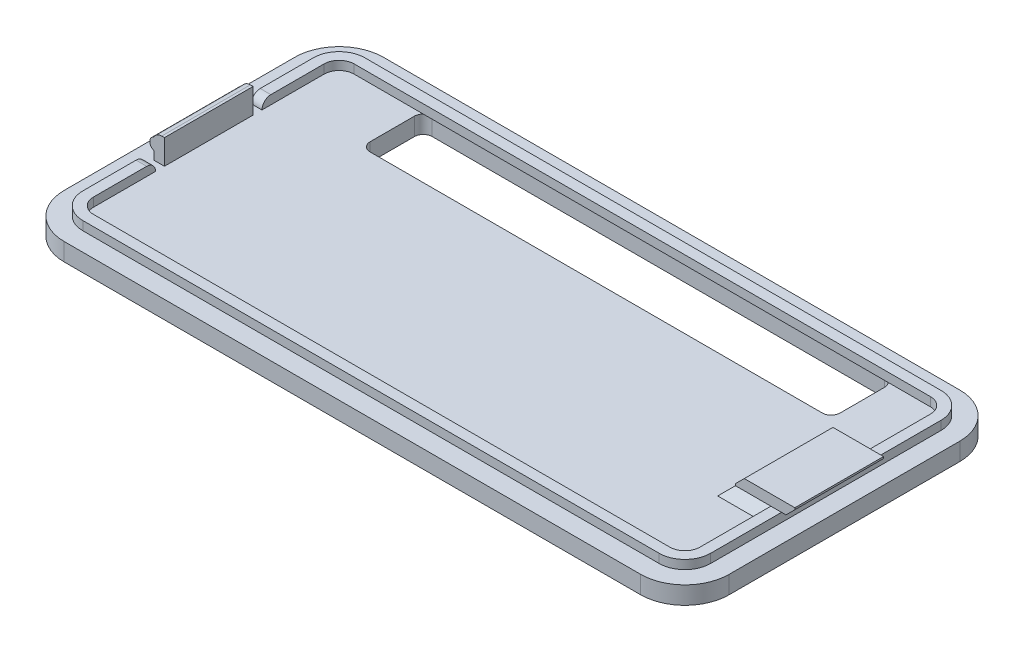
SolidWorks part; units mm, degrees
ref_plane "前视基准面" through (0, 0, 0) normal (0, 0, 1) x (1, 0, 0)
ref_plane "上视基准面" through (0, 0, 0) normal (0, 1, 0) x (1, 0, 0)
ref_plane "右视基准面" through (0, 0, 0) normal (1, 0, 0) x (0, 0, -1)
sketch "zero" plane through (0, 0, 0) normal (0, 1, 0) x (1, 0, 0)
  line L1 (-29.5, 15) -> (29.5, 15)
  line L2 (-32.5, 12) -> (-32.5, -12)
  line L3 (-29.5, -15) -> (29.5, -15)
  line L4 (32.5, 12) -> (32.5, -12)
  line L5 (-32.5, 15) -> (32.5, -15) construction
  line L6 (-32.5, -15) -> (32.5, 15) construction
  line L7 (-25.7, -15) -> (-14.5, -15)
  line L8 (-25.7, -15) -> (-25.7, -9.6569)
  line L9 (-25.7, -9.6569) -> (-14.5, -9.6569)
  line L10 (-14.5, -15) -> (-14.5, -9.6569)
  line L11 (5.2, -15) -> (12.7, -15)
  line L12 (5.2, -15) -> (5.2, -11)
  line L13 (5.2, -11) -> (12.7, -11)
  line L14 (12.7, -15) -> (12.7, -11)
  line L15 (17.8, -15) -> (25.3, -15)
  line L16 (17.8, -15) -> (17.8, -11)
  line L17 (17.8, -11) -> (25.3, -11)
  line L18 (25.3, -15) -> (25.3, -11)
  line L19 (-32.5, 7.7) -> (-19.5, 7.7)
  line L20 (-32.5, 7.7) -> (-32.5, -4.3)
  line L21 (-32.5, -4.3) -> (-19.5, -4.3)
  line L22 (-19.5, 7.7) -> (-19.5, -4.3)
  line L23 (-25.5, 14) -> (25.5, 14)
  line L24 (-25.5, 14) -> (-25.5, 8.8)
  line L25 (-25.5, 8.8) -> (25.5, 8.8)
  line L26 (25.5, 14) -> (25.5, 8.8)
  line L27 (-19.5, 7.2329) -> (-35.5, 7.2329)
  line L28 (-19.5, 7.2329) -> (-19.5, -3.7671)
  line L29 (-19.5, -3.7671) -> (-35.5, -3.7671)
  line L30 (-35.5, 7.2329) -> (-35.5, -3.7671)
  arc A0 (29.5, -15) -> (32.5, -12) centre (29.5, -12) ccw
  arc A1 (29.5, 15) -> (32.5, 12) centre (29.5, 12) cw
  arc A2 (-32.5, -12) -> (-29.5, -15) centre (-29.5, -12) ccw
  arc A3 (-29.5, 15) -> (-32.5, 12) centre (-29.5, 12) ccw
  circle A4 centre (-29, 11.4) radius 3
  circle A5 centre (-29, -11.5) radius 3
  circle A6 centre (29, 11.4) radius 3
  circle A7 centre (29, -11.5) radius 3
  circle A8 centre (-29, 11.4) radius 1.375
  circle A9 centre (-29, -11.5) radius 1.375
  circle A10 centre (29, -11.5) radius 1.375
  circle A11 centre (29, 11.4) radius 1.375
  point P0 (0, 0)
  dimension "D3" = 3
  dimension "D4" = 6
  dimension "D9" = 2.75
  dimension "D1" = 65
  dimension "D2" = 30
  dimension "D5" = 3.6
  dimension "D6" = 3.5
  dimension "D7" = 3.5
  dimension "D8" = 3.5
  dimension "D10" = 12
  dimension "D11" = 7.3
  dimension "D12" = 13
  dimension "D13" = 11.2
  dimension "D14" = 6.8
  dimension "D15" = 19.7
  dimension "D16" = 7.5
  dimension "D17" = 7.5
  dimension "D18" = 5.1
  dimension "D19" = 4
  dimension "D20" = 5.2
  dimension "D21" = 7
  dimension "D22" = 7
  dimension "D23" = 1
  dimension "D24" = 11
  dimension "D25" = 16
sketch "sugar" plane through (0, 0, 0) normal (0, 1, 0) x (1, 0, 0)
  line L1 (-29.5, 15) -> (29.5, 15)
  line L2 (-32.5, 12) -> (-32.5, -12)
  line L3 (-29.5, -15) -> (29.5, -15)
  line L4 (32.5, 12) -> (32.5, -12)
  line L5 (-32.5, 15) -> (32.5, -15) construction
  line L6 (-32.5, -15) -> (32.5, 15) construction
  line L7 (23.5, -11.5) -> (19.5, -11.5)
  line L8 (23.5, -11.5) -> (23.5, -13.9082)
  line L9 (23.5, -13.9082) -> (19.5, -13.9082)
  line L10 (19.5, -11.5) -> (19.5, -13.9082)
  line L11 (16, -11.0071) -> (8.5, -11.0071)
  line L12 (16, -11.0071) -> (16, -15)
  line L13 (16, -15) -> (8.5, -15)
  line L14 (8.5, -11.0071) -> (8.5, -15)
  line L15 (20.5, -13.9082) -> (22.5, -13.9082)
  line L16 (20.5, -13.9082) -> (20.5, -14.8173)
  line L17 (20.5, -14.8173) -> (22.5, -14.8173)
  line L18 (22.5, -13.9082) -> (22.5, -14.8173)
  arc A0 (29.5, 15) -> (32.5, 12) centre (29.5, 12) cw
  arc A1 (29.5, -15) -> (32.5, -12) centre (29.5, -12) ccw
  arc A2 (-32.5, -12) -> (-29.5, -15) centre (-29.5, -12) ccw
  arc A3 (-29.5, 15) -> (-32.5, 12) centre (-29.5, 12) ccw
  circle A4 centre (-29, 11.4) radius 3
  circle A5 centre (-29, 11.4) radius 1.375
  circle A6 centre (-29, -11.5) radius 3
  circle A7 centre (-29, -11.5) radius 1.375
  circle A8 centre (29, 11.4) radius 3
  circle A9 centre (29, 11.4) radius 1.375
  circle A10 centre (29, -11.5) radius 3
  circle A11 centre (29, -11.5) radius 1.375
  dimension "D3" = 3
  dimension "D1" = 65
  dimension "D2" = 30
  dimension "D4" = 9
  dimension "D5" = 4
  dimension "D6" = 3.5
  dimension "D7" = 7.5
  dimension "D8" = 2
  dimension "D9" = 1
sketch "case" plane through (0, 0, 0) normal (0, 1, 0) x (1, 0, 0)
  line L1 (-34.0422, 18) -> (30.9578, 18)
  line L2 (-39.0422, 13) -> (-39.0422, -13)
  line L3 (-34.0422, -18) -> (30.9578, -18)
  line L4 (35.9578, 13) -> (35.9578, -13)
  line L5 (-39.0422, 18) -> (35.9578, -18) construction
  line L6 (-39.0422, -18) -> (35.9578, 18) construction
  arc A0 (-39.0422, -13) -> (-34.0422, -18) centre (-34.0422, -13) ccw
  arc A1 (30.9578, -18) -> (35.9578, -13) centre (30.9578, -13) ccw
  arc A2 (30.9578, 18) -> (35.9578, 13) centre (30.9578, 13) cw
  arc A3 (-34.0422, 18) -> (-39.0422, 13) centre (-34.0422, 13) ccw
  point P0 (-1.5422, 0)
  point P3 (-1.5422, 0)
  dimension "D3" = 5
  dimension "D1" = 75
  dimension "D2" = 36
extrude "凸台-拉伸2" add sketch "case" along normal blind 2
sketch "草图2" plane through (0, 0, 0) normal (0, 1, 0) x (1, 0, 0)
  line L4 (-34.0422, -14.7) -> (30.9578, -14.7)
  line L5 (32.6578, -13) -> (32.6578, 13)
  line L6 (30.9578, 14.7) -> (-34.0422, 14.7)
  line L7 (-35.7422, 13) -> (-35.7422, -13)
  line L8 (33.8578, -13) -> (33.8578, 13)
  line L9 (30.9578, 15.9) -> (-34.0422, 15.9)
  line L10 (-36.9422, 13) -> (-36.9422, -13)
  line L11 (-34.0422, -15.9) -> (30.9578, -15.9)
  line L12 (33.8578, -13) -> (33.8578, 13)
  line L13 (30.9578, 15.9) -> (-34.0422, 15.9)
  line L14 (-36.9422, 13) -> (-36.9422, -13)
  line L15 (-34.0422, -15.9) -> (30.9578, -15.9)
  arc A4 (30.9578, -14.7) -> (32.6578, -13) centre (30.9578, -13) ccw
  arc A5 (32.6578, 13) -> (30.9578, 14.7) centre (30.9578, 13) ccw
  arc A6 (-34.0422, 14.7) -> (-35.7422, 13) centre (-34.0422, 13) ccw
  arc A7 (-35.7422, -13) -> (-34.0422, -14.7) centre (-34.0422, -13) ccw
  arc A8 (30.9578, -15.9) -> (33.8578, -13) centre (30.9578, -13) ccw
  arc A9 (33.8578, 13) -> (30.9578, 15.9) centre (30.9578, 13) ccw
  arc A10 (-34.0422, 15.9) -> (-36.9422, 13) centre (-34.0422, 13) ccw
  arc A11 (-36.9422, -13) -> (-34.0422, -15.9) centre (-34.0422, -13) ccw
  arc A12 (30.9578, -15.9) -> (33.8578, -13) centre (30.9578, -13) ccw
  arc A13 (33.8578, 13) -> (30.9578, 15.9) centre (30.9578, 13) ccw
  arc A14 (-34.0422, 15.9) -> (-36.9422, 13) centre (-34.0422, 13) ccw
  arc A15 (-36.9422, -13) -> (-34.0422, -15.9) centre (-34.0422, -13) ccw
  dimension "D1" = 2.1
  dimension "D2" = 1.2
ref_plane "基准面1" through (0, 2, 0) normal (0, 1, 0) x (1, 0, 0)
sketch "草图3" plane through (0, 2, 0) normal (0, 1, 0) x (1, 0, 0)
  line L4 (-34.0422, -14.7) -> (30.9578, -14.7)
  line L5 (32.6578, -13) -> (32.6578, 13)
  line L6 (30.9578, 14.7) -> (-34.0422, 14.7)
  line L7 (-35.7422, 13) -> (-35.7422, -13)
  line L8 (-34.0422, -14.7) -> (30.9578, -14.7)
  line L9 (32.6578, -13) -> (32.6578, 13)
  line L10 (30.9578, 14.7) -> (-34.0422, 14.7)
  line L11 (-35.7422, 13) -> (-35.7422, -13)
  line L12 (-36.9422, 13) -> (-36.9422, -13)
  line L13 (-34.0422, -15.9) -> (30.9578, -15.9)
  line L14 (33.8578, -13) -> (33.8578, 13)
  line L15 (30.9578, 15.9) -> (-34.0422, 15.9)
  line L16 (-36.9422, 13) -> (-36.9422, -13)
  line L17 (-34.0422, -15.9) -> (30.9578, -15.9)
  line L18 (33.8578, -13) -> (33.8578, 13)
  line L19 (30.9578, 15.9) -> (-34.0422, 15.9)
  arc A4 (30.9578, -14.7) -> (32.6578, -13) centre (30.9578, -13) ccw
  arc A5 (32.6578, 13) -> (30.9578, 14.7) centre (30.9578, 13) ccw
  arc A6 (-34.0422, 14.7) -> (-35.7422, 13) centre (-34.0422, 13) ccw
  arc A7 (-35.7422, -13) -> (-34.0422, -14.7) centre (-34.0422, -13) ccw
  arc A8 (30.9578, -14.7) -> (32.6578, -13) centre (30.9578, -13) ccw
  arc A9 (32.6578, 13) -> (30.9578, 14.7) centre (30.9578, 13) ccw
  arc A10 (-34.0422, 14.7) -> (-35.7422, 13) centre (-34.0422, 13) ccw
  arc A11 (-35.7422, -13) -> (-34.0422, -14.7) centre (-34.0422, -13) ccw
  arc A12 (-36.9422, -13) -> (-34.0422, -15.9) centre (-34.0422, -13) ccw
  arc A13 (30.9578, -15.9) -> (33.8578, -13) centre (30.9578, -13) ccw
  arc A14 (33.8578, 13) -> (30.9578, 15.9) centre (30.9578, 13) ccw
  arc A15 (-34.0422, 15.9) -> (-36.9422, 13) centre (-34.0422, 13) ccw
  arc A16 (-36.9422, -13) -> (-34.0422, -15.9) centre (-34.0422, -13) ccw
  arc A17 (30.9578, -15.9) -> (33.8578, -13) centre (30.9578, -13) ccw
  arc A18 (33.8578, 13) -> (30.9578, 15.9) centre (30.9578, 13) ccw
  arc A19 (-34.0422, 15.9) -> (-36.9422, 13) centre (-34.0422, 13) ccw
  dimension "D1" = 0
  dimension "D2" = 0
extrude "凸台-拉伸4" add sketch "草图3" along normal blind 1
sketch "草图5" plane through (0, 2, 0) normal (0, 1, 0) x (1, 0, 0)
  line L0 (32.6578, -13) -> (32.6578, 13) construction
  line L1 (28.6578, 5) -> (32.6578, 5)
  line L2 (28.6578, 5) -> (28.6578, -5)
  line L3 (28.6578, -5) -> (32.6578, -5)
  line L4 (32.6578, 5) -> (32.6578, -5)
  line L5 (28.6578, 5) -> (32.6578, -5) construction
  line L6 (28.6578, -5) -> (32.6578, 5) construction
  point P0 (30.6578, 0)
  dimension "D2" = 10
  dimension "D3" = 4
  dimension "D4" = 0
extrude "凸台-拉伸6" add sketch "草图5" along normal blind 2.2
ref_plane "基准面3" through (33.8578, 0, 0) normal (1, 0, 0) x (0, 0, -1)
ref_plane "基准面4" through (32.6578, 0, 0) normal (1, 0, 0) x (0, 0, -1)
sketch "草图6" plane through (32.6578, 0, 0) normal (1, 0, 0) x (0, 0, -1)
  line L1 (5, 4.2) -> (-5, 4.2)
  line L2 (5, 4.2) -> (5, 3)
  line L3 (5, 3) -> (-5, 3)
  line L4 (-5, 4.2) -> (-5, 3)
extrude "凸台-拉伸7" add sketch "草图6" along normal blind 2.7
chamfer "倒角1" distance 1 angle 45 1 edges at (35.3578, 3, 0)
chamfer "倒角2" distance 1 angle 45 3 edges at (30.6578, 2, 5) (28.6578, 2, 0) (30.6578, 2, -5)
chamfer "倒角3" distance 1 angle 45 1 edges at (28.6578, 4.2, 0)
sketch "草图7" plane through (0, 2, 0) normal (0, 1, 0) x (1, 0, 0)
  line L0 (-36.9422, 13) -> (-36.9422, -13) construction
  line L1 (-36.9422, 5) -> (-35.7422, 5)
  line L2 (-36.9422, 5) -> (-36.9422, -5)
  line L3 (-36.9422, -5) -> (-35.7422, -5)
  line L4 (-35.7422, 5) -> (-35.7422, -5)
  line L5 (-35.7422, 13) -> (-35.7422, -13) construction
  point P10 (-35.7422, 0)
  dimension "D1" = 5
  dimension "D2" = 10
extrude "凸台-拉伸8" add sketch "草图7" along normal blind 2.8
ref_plane "基准面5" through (0, 0, 5) normal (0, 0, 1) x (1, 0, 0)
sketch "草图8" plane through (0, 0, 5) normal (0, 0, 1) x (1, 0, 0)
  line L0 (-34.0422, 2) -> (-39.0422, 2) construction
  line L1 (-36.9422, 4.8) -> (-36.9422, 3) construction
  circle A0 centre (-36.6922, 3.6) radius 0.7
  dimension "D1" = 1.4
  dimension "D2" = 1.6
  dimension "D3" = 0.25
extrude "凸台-拉伸9" add sketch "草图8" against normal blind 10
fillet "圆角1" radius 1 1 edges at (-36.9422, 4.8, 0)
ref_plane "基准面7" through (-36.9422, 0, 0) normal (-1, 0, 0) x (0, 0, 1)
sketch "草图11" plane through (-36.9422, 0, 0) normal (-1, 0, 0) x (0, 0, 1)
  line L0 (-13, 2) -> (13, 2) construction
  line L1 (5, 3) -> (6, 3)
  line L2 (5, 3) -> (5, 2)
  line L3 (5, 2) -> (6, 2)
  line L4 (6, 3) -> (6, 2)
  line L6 (-5, 3) -> (-6, 3)
  line L7 (-5, 3) -> (-5, 2)
  line L8 (-5, 2) -> (-6, 2)
  line L9 (-6, 3) -> (-6, 2)
  dimension "D1" = 1
  dimension "D2" = 1
extrude "切除-拉伸1" cut sketch "草图11" against normal blind 1.2
fillet "圆角2" radius 1 2 edges at (-36.3422, 3, 6) (-36.3422, 3, -6)
ref_plane "基准面8" through (0, 0, 0) normal (0, -1, 0) x (-1, 0, 0)
sketch "草图12" plane through (0, 0, 0) normal (0, -1, 0) x (-1, 0, 0)
  line L76 (34.0422, -18) -> (-30.9578, -18) construction
  line L78 (39.0422, 13) -> (39.0422, -13) construction
  line B0 (-8.1993, 1.426) -> (-9.0198, 1.899)
  line B1 (-9.0198, 1.899) -> (-13.2767, 4.3551)
  line B2 (-13.2767, 4.3551) -> (-14.0973, 4.8339)
  line B3 (-15.8183, 4.8339) -> (-16.6389, 4.3551)
  line B4 (-16.6389, 4.3551) -> (-20.8958, 1.899)
  line B5 (-20.8958, 1.899) -> (-21.7165, 1.426)
  line B6 (-22.577, -0.0613) -> (-22.577, -6.8769)
  line B7 (-21.7165, -8.3643) -> (-20.8958, -8.8373)
  line B8 (-20.8958, -8.8373) -> (-16.6389, -11.2934)
  line B9 (-16.6389, -11.2934) -> (-15.8183, -11.772)
  line B10 (-14.0973, -11.772) -> (-13.2767, -11.2934)
  line B11 (-13.2767, -11.2934) -> (-9.0198, -8.8373)
  line B12 (-9.0198, -8.8373) -> (-8.1993, -8.3643)
  line B13 (-7.3388, -6.8769) -> (-7.3388, -0.0613)
  line B14 (-20.6223, 0.7479) -> (-15.3568, 3.791)
  line B15 (-14.5532, 3.791) -> (-9.3162, 0.7422)
  line B16 (-9.3105, 0.0413) -> (-14.3993, -3.0018)
  line B17 (-12.8208, -8.1591) -> (-13.4135, -8.4896)
  line B18 (-13.4705, -8.5865) -> (-13.4705, -10.2961)
  line B19 (-13.5274, -10.393) -> (-14.633, -11.0198)
  line B20 (-14.7983, -10.9229) -> (-14.7983, -5.646)
  line B21 (-14.7413, -5.5491) -> (-12.8607, -4.4835)
  line B22 (-8.9173, -7.8058) -> (-10.0114, -8.4269)
  line B23 (-10.1767, -8.3301) -> (-10.1767, -5.8169)
  line B24 (-10.1197, -5.7201) -> (-9.0256, -5.1046)
  line B25 (-8.8603, -5.2015) -> (-8.8603, -7.7089)
  line B26 (-12.8893, -7.1447) -> (-13.4135, -7.4069)
  line B27 (-13.4705, -7.2872) -> (-13.4705, -5.9423)
  line B28 (-13.4135, -5.8455) -> (-12.9234, -5.5719)
  line B29 (-3.344, -0.54) -> (-5.2189, -0.54)
  line B30 (-5.2189, -0.54) -> (-5.2189, -7.1048)
  line B31 (-5.2189, -7.1048) -> (-4.3868, -7.1048)
  line B32 (-4.3868, -7.1048) -> (-4.3868, -4.5005)
  line B33 (-4.3868, -4.5005) -> (-3.2984, -4.5005)
  line B34 (-3.4066, -3.8281) -> (-4.3868, -3.8281)
  line B35 (-4.3868, -3.8281) -> (-4.3868, -1.2124)
  line B36 (-4.3868, -1.2124) -> (-3.4408, -1.2124)
  line B37 (0.1948, -2.2382) -> (0.1948, -7.1048)
  line B38 (0.1948, -7.1048) -> (1.0098, -7.1048)
  line B39 (1.0098, -7.1048) -> (1.0098, -2.2382)
  line B40 (1.0098, -2.2382) -> (0.1948, -2.2382)
  line B41 (5.7169, -3.3153) -> (4.8849, -2.9847)
  line B42 (6.0417, -2.1983) -> (6.8396, -1.1953)
  line B43 (3.6084, -4.1586) -> (4.4575, -4.5177)
  line B44 (2.9074, -5.1673) -> (2.0014, -6.2729)
  line B45 (10.8229, -2.0102) -> (10.8229, -5.3497)
  line B46 (9.3811, -4.9621) -> (9.3811, -2.0102)
  line B47 (9.3811, -2.0102) -> (7.7912, -2.0102)
  line B48 (7.7912, -2.0102) -> (7.7912, -5.1616)
  line B49 (10.9711, -6.4039) -> (11.0052, -6.4039)
  line B50 (11.0052, -6.4039) -> (11.1193, -7.1048)
  line B51 (11.1193, -7.1048) -> (12.4185, -7.1048)
  line B52 (12.4185, -7.1048) -> (12.4185, -2.0102)
  line B53 (12.4185, -2.0102) -> (10.8229, -2.0102)
  line B54 (16.2708, -6.1019) -> (15.4673, -6.1019)
  line B55 (17.365, -3.1614) -> (18.1513, -3.1614)
  line B56 (18.1513, -3.1614) -> (18.1513, -2.0102)
  line B57 (18.1513, -2.0102) -> (16.2822, -2.0102)
  line B58 (14.0312, -5.0533) -> (14.0312, -5.0875)
  line B59 (13.9344, -6.9168) -> (13.9344, -6.9624)
  line B60 (15.4844, -7.3214) -> (15.9688, -7.3214)
  line B61 (18.6072, -2.5516) -> (19.1657, -3.6002)
  line B62 (21.411, -6.592) -> (21.4508, -6.592)
  line B63 (21.4508, -6.592) -> (21.5648, -7.1048)
  line B64 (21.5648, -7.1048) -> (22.8641, -7.1048)
  line B65 (22.8641, -7.1048) -> (22.8641, -4.2099)
  line B66 (21.2685, -4.7741) -> (21.2685, -5.589)
  line B67 (25.3545, -2.8935) -> (25.3203, -2.8935)
  line B68 (25.3203, -2.8935) -> (25.212, -2.0102)
  line B69 (25.212, -2.0102) -> (23.9127, -2.0102)
  line B70 (23.9127, -2.0102) -> (23.9127, -7.1048)
  line B71 (23.9127, -7.1048) -> (25.4969, -7.1048)
  line B72 (25.4969, -7.1048) -> (25.4969, -4.1928)
  line B73 (27.1552, -3.3608) -> (27.423, -1.9875)
  line B74 (-13.4135, -7.4069) -> (-13.4135, -8.4896)
  line B75 (-13.4705, -7.2872) -> (-13.4705, -8.5865)
  spline B76 degree 3 poles (-14.0973, 4.8339) (-14.3652, 4.982) (-14.6615, 5.0618) (-14.9578, 5.0618) knots 3 3 3 3 4 4 4 4
  spline B77 degree 3 poles (-14.9578, 5.0618) (-15.2541, 5.0618) (-15.5505, 4.982) (-15.8183, 4.8339) knots 4 4 4 4 5 5 5 5
  spline B78 degree 3 poles (-21.7165, 1.426) (-22.2464, 1.1183) (-22.577, 0.5485) (-22.577, -0.0613) knots 8 8 8 8 9 9 9 9
  spline B79 degree 3 poles (-22.577, -6.8769) (-22.577, -7.4923) (-22.2464, -8.0565) (-21.7165, -8.3643) knots 10 10 10 10 11 11 11 11
  spline B80 degree 3 poles (-15.8183, -11.772) (-15.5505, -11.9259) (-15.2541, -12) (-14.9578, -12) knots 14 14 14 14 15 15 15 15
  spline B81 degree 3 poles (-14.9578, -12) (-14.6615, -12) (-14.3652, -11.9259) (-14.0973, -11.772) knots 15 15 15 15 16 16 16 16
  spline B82 degree 3 poles (-8.1993, -8.3643) (-7.6636, -8.0565) (-7.3388, -7.4923) (-7.3388, -6.8769) knots 19 19 19 19 20 20 20 20
  spline B83 degree 3 poles (-7.3388, -0.0613) (-7.3388, 0.5485) (-7.6636, 1.1183) (-8.1993, 1.426) knots 21 21 21 21 22 22 22 22
  spline B84 degree 2 poles (-15.5106, -3.0018) (-20.6622, -0.0271) (-20.6736, -0.0214) knots 0 0 0 1 1 1
  spline B85 degree 3 poles (-20.6736, -0.0214) (-20.9414, 0.1723) (-20.9129, 0.5826) (-20.6223, 0.7479) knots 1 1 1 1 2 2 2 2
  spline B86 degree 3 poles (-15.3568, 3.791) (-15.1117, 3.9335) (-14.8039, 3.9335) (-14.5532, 3.791) knots 3 3 3 3 4 4 4 4
  spline B87 degree 3 poles (-9.3162, 0.7422) (-9.0484, 0.5883) (-9.0427, 0.2008) (-9.3105, 0.0413) knots 5 5 5 5 6 6 6 6
  spline B88 degree 3 poles (-14.3993, -3.0018) (-14.7413, -3.2013) (-15.1687, -3.2013) (-15.5106, -3.0018) knots 7 7 7 7 8 8 8 8
  spline B89 degree 3 poles (-13.4705, -10.2961) (-13.4705, -10.336) (-13.4876, -10.3702) (-13.5274, -10.393) knots 3 3 3 3 4 4 4 4
  spline B90 degree 3 poles (-14.633, -11.0198) (-14.7071, -11.0597) (-14.7983, -11.0084) (-14.7983, -10.9229) knots 5 5 5 5 6 6 6 6
  spline B91 degree 3 poles (-14.7983, -5.646) (-14.7983, -5.6061) (-14.7812, -5.5662) (-14.7413, -5.5491) knots 7 7 7 7 8 8 8 8
  spline B92 degree 3 poles (-12.8607, -4.4835) (-11.6412, -3.7939) (-10.6326, -3.6572) (-10.6326, -5.0249) knots 9 9 9 9 10 10 10 10
  spline B93 degree 3 poles (-10.6326, -5.0249) (-10.6326, -6.3412) (-11.6526, -7.498) (-12.8208, -8.1591) knots 10 10 10 10 11 11 11 11
  spline B94 degree 3 poles (-8.8603, -7.7089) (-8.8603, -7.7488) (-8.8831, -7.7887) (-8.9173, -7.8058) knots 0 0 0 0 1 1 1 1
  spline B95 degree 3 poles (-10.0114, -8.4269) (-10.0855, -8.4668) (-10.1767, -8.4155) (-10.1767, -8.3301) knots 2 2 2 2 3 3 3 3
  spline B96 degree 3 poles (-10.1767, -5.8169) (-10.1767, -5.7771) (-10.1539, -5.7429) (-10.1197, -5.7201) knots 4 4 4 4 5 5 5 5
  spline B97 degree 3 poles (-9.0256, -5.1046) (-8.9515, -5.0647) (-8.8603, -5.116) (-8.8603, -5.2015) knots 6 6 6 6 7 7 7 7
  spline B98 degree 3 poles (-9.5156, -3.4349) (-9.0768, -3.1842) (-8.7634, -3.2924) (-8.7634, -3.6914) (-8.7634, -4.0846) (-9.0768, -4.5461) (-9.5156, -4.7912) knots 2 2 2 2 3 3 3 4 4 4 4
  spline B99 degree 3 poles (-9.5156, -4.7912) (-9.9601, -5.0476) (-10.2735, -4.9394) (-10.2735, -4.5461) (-10.2735, -4.1415) (-9.9601, -3.6856) (-9.5156, -3.4349) knots 0 0 0 0 1 1 1 2 2 2 2
  spline B100 degree 3 poles (-11.9319, -5.76) (-11.9319, -6.3013) (-12.2395, -6.78) (-12.8893, -7.1447) knots 0 0 0 0 1 1 1 1
  spline B101 degree 3 poles (-13.4705, -5.9423) (-13.4705, -5.9024) (-13.4477, -5.8625) (-13.4135, -5.8455) knots 4 4 4 4 5 5 5 5
  spline B102 degree 3 poles (-12.9234, -5.5719) (-12.2852, -5.2072) (-11.9319, -5.2015) (-11.9319, -5.76) knots 6 6 6 6 7 7 7 7
  spline B103 degree 3 poles (-3.2984, -4.5005) (-1.868, -4.5005) (-0.8822, -3.8509) (-0.8822, -2.4661) knots 5 5 5 5 6 6 6 6
  spline B104 degree 3 poles (-0.8822, -2.4661) (-0.8822, -1.0301) (-1.868, -0.54) (-3.344, -0.54) knots 6 6 6 6 7 7 7 7
  spline B105 degree 3 poles (-3.4408, -1.2124) (-2.2897, -1.2124) (-1.7084, -1.5145) (-1.7084, -2.4661) knots 3 3 3 3 4 4 4 4
  spline B106 degree 3 poles (-1.7084, -2.4661) (-1.7084, -3.4064) (-2.2498, -3.8281) (-3.4066, -3.8281) knots 4 4 4 4 5 5 5 5
  spline B107 degree 3 poles (0.6052, -1.2352) (0.93, -1.2352) (1.1694, -1.013) (1.1694, -0.711) (1.1694, -0.3747) (0.93, -0.181) (0.6052, -0.181) knots 2 2 2 2 3 3 3 4 4 4 4
  spline B108 degree 3 poles (0.6052, -0.181) (0.2804, -0.181) (0.041, -0.3747) (0.041, -0.711) (0.041, -1.013) (0.2804, -1.2352) (0.6052, -1.2352) knots 0 0 0 0 1 1 1 2 2 2 2
  spline B109 degree 3 poles (4.8849, -2.9847) (4.2979, -2.7511) (3.8762, -2.6086) (3.8762, -2.2382) knots 1 1 1 1 2 2 2 2
  spline B110 degree 3 poles (3.8762, -2.2382) (3.8762, -1.8849) (4.1783, -1.6854) (4.674, -1.6854) knots 2 2 2 2 3 3 3 3
  spline B111 degree 3 poles (4.674, -1.6854) (5.1926, -1.6854) (5.6029, -1.8621) (6.0417, -2.1983) knots 3 3 3 3 4 4 4 4
  spline B112 degree 3 poles (6.8396, -1.1953) (6.2583, -0.6084) (5.4433, -0.3121) (4.674, -0.3121) knots 5 5 5 5 6 6 6 6
  spline B113 degree 3 poles (4.674, -0.3121) (3.2551, -0.3121) (2.2521, -1.2124) (2.2521, -2.3294) knots 6 6 6 6 7 7 7 7
  spline B114 degree 3 poles (2.2521, -2.3294) (2.2521, -3.2981) (2.9074, -3.8794) (3.6084, -4.1586) knots 7 7 7 7 8 8 8 8
  spline B115 degree 3 poles (4.4575, -4.5177) (5.0274, -4.757) (5.3978, -4.8824) (5.3978, -5.2699) knots 9 9 9 9 10 10 10 10
  spline B116 degree 3 poles (5.3978, -5.2699) (5.3978, -5.6289) (5.1185, -5.8511) (4.5259, -5.8511) knots 10 10 10 10 11 11 11 11
  spline B117 degree 3 poles (4.5259, -5.8511) (4.0016, -5.8511) (3.3804, -5.5719) (2.9074, -5.1673) knots 11 11 11 11 12 12 12 12
  spline B118 degree 3 poles (2.0014, -6.2729) (2.6909, -6.9054) (3.6254, -7.2302) (4.4916, -7.2302) knots 13 13 13 13 14 14 14 14
  spline B119 degree 3 poles (4.4916, -7.2302) (6.1044, -7.2302) (7.0389, -6.2557) (7.0389, -5.1445) knots 14 14 14 14 15 15 15 15
  spline B120 degree 3 poles (7.0389, -5.1445) (7.0389, -4.2042) (6.5432, -3.6458) (5.7169, -3.3153) knots 15 15 15 15 16 16 16 16
  spline B121 degree 3 poles (10.8229, -5.3497) (10.5551, -5.7258) (10.3328, -5.8682) (9.9738, -5.8682) knots 1 1 1 1 2 2 2 2
  spline B122 degree 3 poles (9.9738, -5.8682) (9.5692, -5.8682) (9.3811, -5.6688) (9.3811, -4.9621) knots 2 2 2 2 3 3 3 3
  spline B123 degree 3 poles (7.7912, -5.1616) (7.7912, -6.4324) (8.2642, -7.2302) (9.3754, -7.2302) knots 6 6 6 6 7 7 7 7
  spline B124 degree 3 poles (9.3754, -7.2302) (10.0706, -7.2302) (10.5494, -6.9054) (10.9711, -6.4039) knots 7 7 7 7 8 8 8 8
  spline B125 degree 3 poles (15.4673, -6.1019) (14.9202, -6.1019) (14.7151, -5.9936) (14.7151, -5.76) knots 1 1 1 1 2 2 2 2
  spline B126 degree 3 poles (14.7151, -5.76) (14.7151, -5.589) (14.7549, -5.5092) (14.8746, -5.4009) knots 2 2 2 2 3 3 3 3
  spline B127 degree 3 poles (14.8746, -5.4009) (15.0969, -5.4636) (15.302, -5.4921) (15.473, -5.4921) knots 3 3 3 3 4 4 4 4
  spline B128 degree 3 poles (15.473, -5.4921) (16.6013, -5.4921) (17.5074, -4.9735) (17.5074, -3.7825) knots 4 4 4 4 5 5 5 5
  spline B129 degree 3 poles (17.5074, -3.7825) (17.5074, -3.5375) (17.4447, -3.3038) (17.365, -3.1614) knots 5 5 5 5 6 6 6 6
  spline B130 degree 3 poles (16.2822, -2.0102) (16.0485, -1.9248) (15.7693, -1.8849) (15.473, -1.8849) knots 9 9 9 9 10 10 10 10
  spline B131 degree 3 poles (15.473, -1.8849) (14.3732, -1.8849) (13.3417, -2.4889) (13.3417, -3.7369) knots 10 10 10 10 11 11 11 11
  spline B132 degree 3 poles (13.3417, -3.7369) (13.3417, -4.3296) (13.6722, -4.8026) (14.0312, -5.0533) knots 11 11 11 11 12 12 12 12
  spline B133 degree 3 poles (14.0312, -5.0875) (13.7007, -5.3212) (13.467, -5.6802) (13.467, -6.0392) knots 13 13 13 13 14 14 14 14
  spline B134 degree 3 poles (13.467, -6.0392) (13.467, -6.4666) (13.6665, -6.7344) (13.9344, -6.9168) knots 14 14 14 14 15 15 15 15
  spline B135 degree 3 poles (13.9344, -6.9624) (13.4613, -7.2017) (13.2106, -7.5436) (13.2106, -7.9653) knots 16 16 16 16 17 17 17 17
  spline B136 degree 3 poles (13.2106, -7.9653) (13.2106, -8.8771) (14.1737, -9.2475) (15.3476, -9.2475) knots 17 17 17 17 18 18 18 18
  spline B137 degree 3 poles (15.3476, -9.2475) (17.1199, -9.2475) (18.2312, -8.4839) (18.2312, -7.4069) knots 18 18 18 18 19 19 19 19
  spline B138 degree 3 poles (18.2312, -7.4069) (18.2312, -6.4837) (17.5245, -6.1019) (16.2708, -6.1019) knots 19 19 19 19 20 20 20 20
  spline B139 degree 3 poles (15.473, -4.5347) (15.1083, -4.5347) (14.8291, -4.2669) (14.8291, -3.7369) (14.8291, -3.2184) (15.1083, -2.9505) (15.473, -2.9505) knots 2 2 2 2 3 3 3 4 4 4 4
  spline B140 degree 3 poles (15.473, -2.9505) (15.8491, -2.9505) (16.1169, -3.2184) (16.1169, -3.7369) (16.1169, -4.2669) (15.8491, -4.5347) (15.473, -4.5347) knots 0 0 0 0 1 1 1 2 2 2 2
  spline B141 degree 3 poles (15.5983, -8.2503) (14.943, -8.2503) (14.5156, -8.0736) (14.5156, -7.7146) knots 0 0 0 0 1 1 1 1
  spline B142 degree 3 poles (14.5156, -7.7146) (14.5156, -7.5436) (14.5953, -7.4012) (14.7549, -7.2587) knots 1 1 1 1 2 2 2 2
  spline B143 degree 3 poles (14.7549, -7.2587) (14.9202, -7.3043) (15.114, -7.3214) (15.4844, -7.3214) knots 2 2 2 2 3 3 3 3
  spline B144 degree 3 poles (15.9688, -7.3214) (16.4417, -7.3214) (16.7096, -7.3841) (16.7096, -7.6861) knots 4 4 4 4 5 5 5 5
  spline B145 degree 3 poles (16.7096, -7.6861) (16.7096, -8.0109) (16.2537, -8.2503) (15.5983, -8.2503) knots 5 5 5 5 6 6 6 6
  spline B146 degree 3 poles (20.8013, -1.8849) (20.0091, -1.8849) (19.2797, -2.1527) (18.6072, -2.5516) knots 0 0 0 0 1 1 1 1
  spline B147 degree 3 poles (19.1657, -3.6002) (19.6729, -3.3153) (20.0946, -3.1557) (20.4992, -3.1557) knots 2 2 2 2 3 3 3 3
  spline B148 degree 3 poles (20.4992, -3.1557) (21.0177, -3.1557) (21.2344, -3.395) (21.2685, -3.8053) knots 3 3 3 3 4 4 4 4
  spline B149 degree 3 poles (21.2685, -3.8053) (19.2797, -4.0219) (18.4362, -4.6031) (18.4362, -5.6802) knots 4 4 4 4 5 5 5 5
  spline B150 degree 3 poles (18.4362, -5.6802) (18.4362, -6.5293) (19.0118, -7.2302) (19.9522, -7.2302) knots 5 5 5 5 6 6 6 6
  spline B151 degree 3 poles (19.9522, -7.2302) (20.5163, -7.2302) (20.9893, -6.9681) (21.411, -6.592) knots 6 6 6 6 7 7 7 7
  spline B152 degree 3 poles (22.8641, -4.2099) (22.8641, -2.6143) (22.1176, -1.8849) (20.8013, -1.8849) knots 11 11 11 11 12 12 12 12
  spline B153 degree 3 poles (21.2685, -5.589) (21.0349, -5.8398) (20.824, -5.9936) (20.4992, -5.9936) knots 0 0 0 0 1 1 1 1
  spline B154 degree 3 poles (20.4992, -5.9936) (20.1686, -5.9936) (19.9522, -5.8511) (19.9522, -5.5548) knots 1 1 1 1 2 2 2 2
  spline B155 degree 3 poles (19.9522, -5.5548) (19.9522, -5.1958) (20.277, -4.9109) (21.2685, -4.7741) knots 2 2 2 2 3 3 3 3
  spline B156 degree 3 poles (26.8076, -1.8849) (26.2947, -1.8849) (25.7305, -2.2154) (25.3545, -2.8935) knots 0 0 0 0 1 1 1 1
  spline B157 degree 3 poles (25.4969, -4.1928) (25.7648, -3.5204) (26.2207, -3.2811) (26.5967, -3.2811) knots 7 7 7 7 8 8 8 8
  spline B158 degree 3 poles (26.5967, -3.2811) (26.8247, -3.2811) (26.9729, -3.3153) (27.1552, -3.3608) knots 8 8 8 8 9 9 9 9
  spline B159 degree 3 poles (27.423, -1.9875) (27.2806, -1.9248) (27.1096, -1.8849) (26.8076, -1.8849) knots 10 10 10 10 11 11 11 11
  dimension "D1" = 6
  dimension "D2" = 54
sketch_block_instance "块1-1"
sketch_block "块1"
extrude "切除-拉伸2" cut sketch "草图12" against normal blind 0.5
sketch "草图13" plane through (0, 0, 0) normal (0, 1, 0) x (1, 0, 0)
  line L0 (30.9578, 18) -> (-34.0422, 18) construction
  line L1 (-26.5422, 15) -> (26.4578, 15)
  line L2 (-26.5422, 15) -> (-26.5422, 8)
  line L3 (-26.5422, 8) -> (26.4578, 8)
  line L4 (26.4578, 15) -> (26.4578, 8)
  line L5 (35.9578, -13) -> (35.9578, 13) construction
  dimension "D1" = 7
  dimension "D2" = 53
  dimension "D3" = 3
  dimension "D4" = 9.5
extrude "切除-拉伸3" cut sketch "草图13" along normal blind 2
fillet "圆角3" radius 1 4 edges at (-26.5422, 1, -15) (-26.5422, 1, -8) (26.4578, 1, -15) (26.4578, 1, -8)
